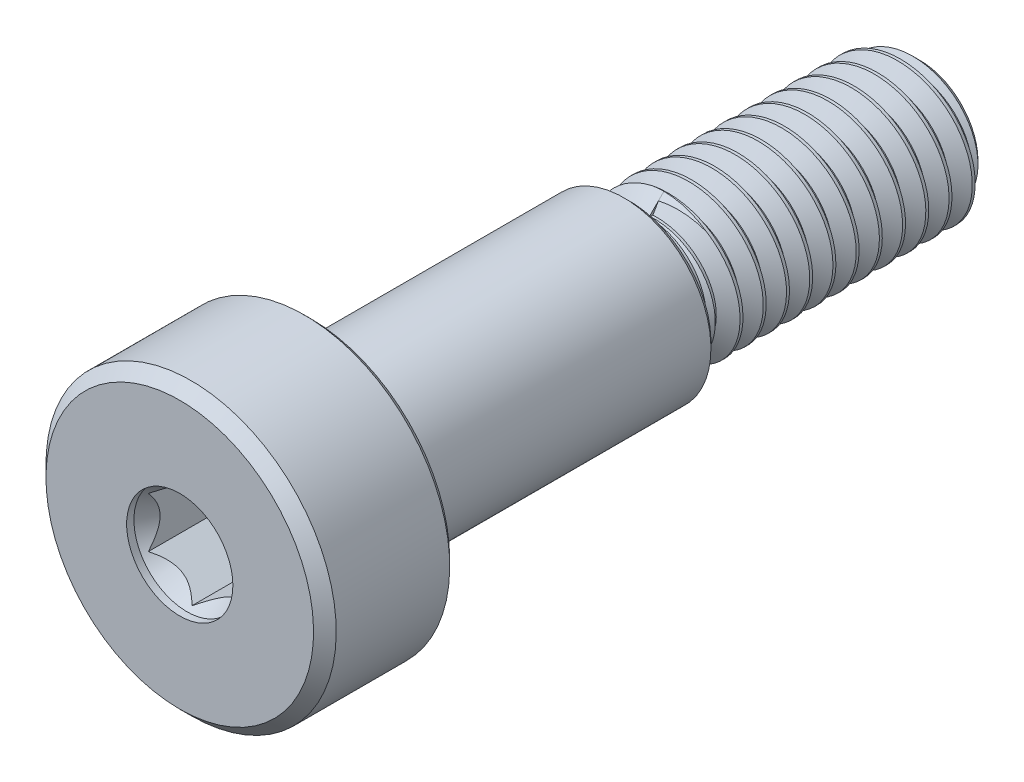
SolidWorks part; units mm, degrees
ref_plane "Front Plane" through (0, 0, 0) normal (0, 0, 1) x (1, 0, 0)
ref_plane "Top Plane" through (0, 0, 0) normal (0, 1, 0) x (1, 0, 0)
ref_plane "Right Plane" through (0, 0, 0) normal (1, 0, 0) x (0, 0, -1)
sketch "Sketch1" plane through (0, 0, 0) normal (1, 0, 0) x (0, 0, -1)
  line L0 (-12.75, 0) -> (12.75, 0) construction
  line L1 (-12.75, -5) -> (-12.75, 5)
  line L2 (-8.25, -5) -> (-8.25, 5)
  line L3 (2.75, 3) -> (2.75, -3)
  line L4 (-12.75, 1.5) -> (-12.75, -1.5)
  line L5 (12.75, 2.5) -> (12.75, -2.5)
  line L6 (12.7, 2.5866) -> (13.5, 2.5866) construction
  line L7 (13.5, 2.5866) -> (13.1, 1.8938) construction
  line L8 (13.1, 1.8938) -> (12.7, 2.5866) construction
  line L9 (13.1, 2.5866) -> (13.1, 2.5) construction
  line L10 (13.1, 1.8938) -> (13.1, 1.9804) construction
  line L11 (12.75, 2.5) -> (13.45, 2.5) construction
  line L12 (12.725, 2.5433) -> (13.475, 2.5433) construction
  line L13 (13.05, 1.9804) -> (13.15, 1.9804) construction
  line L14 (-8.25, 0) -> (-7.15, 0) construction
  line L15 (-7.15, 0) -> (1.65, 0) construction
  line L16 (1.65, 0) -> (2.75, 0) construction
  point P0 (9.95, -2.5)
  point P4 (0, 0)
  point P8 (-12.75, 0)
  point P11 (-8.25, 0)
  point P14 (2.75, 0)
  point P17 (-12.75, 0)
  point P20 (12.75, 0)
  point P28 (13.1, 2.5)
  point P32 (13.1, 2.5433)
  point P35 (13.1, 1.9804)
  point P36 (12.75, 3)
  dimension "D1" = 2.8
  dimension "D3" = 0.1
  dimension "D2" = 8.8
sketch "Sketch2" plane through (0, 0, 0) normal (1, 0, 0) x (0, 0, -1)
  line L0 (12.75, 0) -> (12.75, 2)
  line L2 (12.75, 2) -> (12.25, 2.5)
  line L3 (12.25, 2.5) -> (3.9294, 2.5)
  line L4 (3.9294, 2.5) -> (3.4098, 1.9804)
  line L5 (3.4098, 1.9804) -> (3.0098, 1.9804)
  line L6 (13.1, 1.8938) -> (12.7, 2.5866) construction
  line L7 (2.75, 2.2402) -> (2.75, 2.8)
  line L8 (2.55, 3) -> (-7.1868, 3)
  line L9 (-7.1868, 3) -> (-7.5388, 2.7968)
  line L10 (-7.5388, 2.7968) -> (-7.6277, 2.7968)
  line L11 (-8.25, -5) -> (-8.25, 5) construction
  line L12 (-12.75, -5) -> (-12.75, 5) construction
  line L13 (-8.45, 5) -> (-12.3595, 5)
  line L14 (-12.75, 4.6095) -> (-12.75, 0)
  line L15 (-12.75, 0) -> (12.75, 0)
  line L16 (-12.3595, 5) -> (-12.75, 4.6095)
  line L17 (-8.25, 4.8) -> (-8.25, 3.4191)
  line L18 (2.55, 3) -> (2.75, 2.8)
  line L19 (2.75, 3) -> (2.75, -3) construction
  line L20 (-8.45, 5) -> (-8.25, 4.8)
  arc A0 (3.0098, 1.9804) -> (2.75, 2.2402) centre (3.0098, 2.2402) cw
  arc A1 (-7.6277, 2.7968) -> (-8.25, 3.4191) centre (-7.6277, 3.4191) cw
  point P23 (12.9, 2.2402)
  dimension "D4" = 0.4
  dimension "D6" = 30
  dimension "D7" = 0.2032
  dimension "D8" = 0.3905
  dimension "D11" = 0.2
  dimension "D3" = 45
  dimension "D9" = 0.2
  dimension "D10" = 0.0889
  dimension "D5" = 0.7112
  dimension "D2" = 0.5
revolve "Revolve1" add sketch "Sketch2" angle 360 about L15
sketch "Sketch3" plane through (0, 0, 12.75) normal (0, 0, 1) x (1, 0, 0)
  line L1 (0, 1.7321) -> (-1.5, 0.866)
  line L2 (-1.5, 0.866) -> (-1.5, -0.866)
  line L3 (-1.5, -0.866) -> (0, -1.7321)
  line L4 (0, -1.7321) -> (1.5, -0.866)
  line L5 (1.5, -0.866) -> (1.5, 0.866)
  line L6 (1.5, 0.866) -> (0, 1.7321)
  circle A0 centre (0, 0) radius 1.5 construction
  circle A1 centre (0, 0) radius 5 construction
  circle A2 centre (0, 0) radius 5 construction
extrude "Cut-Extrude1" cut sketch "Sketch3" against normal blind 2.5
sketch "Sketch4" plane through (0, 0, 12.75) normal (0, 0, 1) x (1, 0, 0)
  circle A0 centre (0, 0) radius 1.83
  dimension "D1" = 3.66
extrude "Cut-Extrude2" cut sketch "Sketch4" against normal blind 0.25
extrude "Cut-Extrude3" cut sketch "Sketch4<2>" against normal blind 1.875 draft 30 from surface starting at face at (1.83, 0, 12.5)
sketch "Sketch4<2>" plane through (0, 0, 12.75) normal (0, 0, 1) x (1, 0, 0) same geometry as "Sketch4"
ref_axis "Center Axis 1" through (0, 0, 17.3428) along (0, 0, -1)
ref_plane "Contact Plane 1" through (0, 0, 8.25) normal (0, 0, -1) x (-1, 0, 0)
sketch "Sketch5" plane through (0, 0, -12.75) normal (0, 0, -1) x (-1, 0, 0)
  circle A0 centre (0, 0) radius 2.5
curve "Helix/Spiral1" pitch 0.8 height 9.6 radius 2.5 centre (0, 0, -12.75) axis (0, 0, 1) start towards (0, 1, 0)
sketch "Sketch6" plane through (0, 0, 0) normal (1, 0, 0) x (0, 0, -1)
  line L0 (12.725, 2.5433) -> (13.475, 2.5433)
  line L1 (13.475, 2.5433) -> (13.15, 1.9804)
  line L2 (13.15, 1.9804) -> (13.05, 1.9804)
  line L3 (13.05, 1.9804) -> (12.725, 2.5433)
sweep "Cut-Sweep1" cut profiles "Sketch6" path "Helix/Spiral1"
equation "\"D3@Sketch1\" = \"Thread Pitch@Sketch1\" / 8"
equation "\"D1@Sketch1\" = \"Thread Pitch@Sketch1\" * 3.5"
equation "\"D4@Sketch2\" = \"Thread Pitch@Sketch1\" / 2"
equation "\"D8@Sketch2\"=\"Thread Size@Sketch1\" * .0781"
equation "\"D11@Sketch2\"=\"Thread Pitch@Sketch1\" * .25"
equation "\"D1@Cut-Extrude1\" = \"Thread Size@Sketch1\" * .5"
equation "\"D1@Cut-Extrude2\"=\"D1@Cut-Extrude1\" * .1"
equation "\"D4@Helix/Spiral1\" = \"Thread Pitch@Sketch1\""
equation "\"D3@Helix/Spiral1\" = \"Thread Length@Sketch1\" - ( \"Thread Pitch@Sketch1\" / 2 )"
equation "\"D2@Sketch1\"=\"Shoulder Length@Sketch1\"*.80"
equation "\"D1@Sketch4\"=\"Drive Size@Sketch1\" * 1.22"
equation "\"D9@Sketch2\" = \"Thread Size@Sketch1\" * .04"
equation "\"D10@Sketch2\"=\"D5@Sketch2\"*.125"
equation "\"D1@Cut-Extrude3\" = \"D1@Cut-Extrude1\" * .75"
equation "\"D2@Sketch2\"=\"Thread Pitch@Sketch1\"*.625"
